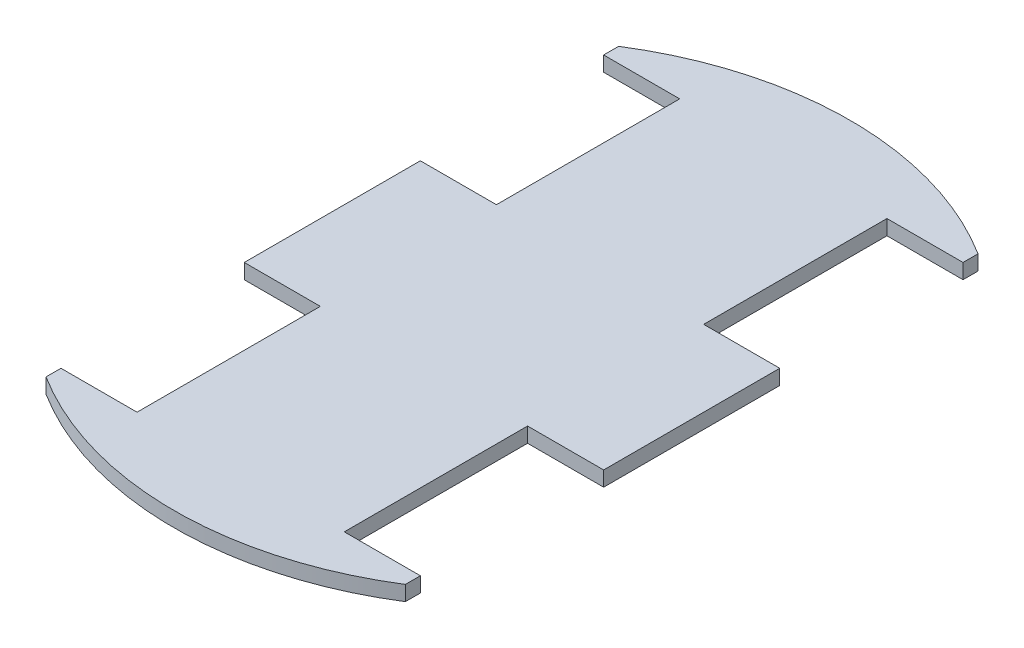
SolidWorks part; units mm, degrees
material "Oak"
ref_plane "Front Plane" through (0, 0, 0) normal (0, 0, 1) x (1, 0, 0)
ref_plane "Top Plane" through (0, 0, 0) normal (0, 1, 0) x (1, 0, 0)
ref_plane "Right Plane" through (0, 0, 0) normal (1, 0, 0) x (0, 0, -1)
sketch "Sketch1" plane through (0, 0, 0) normal (0, 1, 0) x (1, 0, 0)
  line L0 (50.292, 32.512) -> (76.2, 32.512) construction
  line L1 (-76.2, 32.512) -> (-50.292, 32.512) construction
  line L2 (-76.2, 32.512) -> (-76.2, -32.512) construction
  line L3 (-76.2, -32.512) -> (-50.292, -32.512) construction
  line L4 (-50.292, 32.512) -> (-50.292, -32.512) construction
  line L5 (-76.2, 32.512) -> (-50.292, -32.512) construction
  line L6 (-76.2, -32.512) -> (-50.292, 32.512) construction
  line L7 (50.292, 32.512) -> (50.292, -32.512) construction
  line L8 (50.292, -32.512) -> (76.2, -32.512) construction
  line L9 (76.2, 32.512) -> (76.2, -32.512) construction
  line L10 (50.292, 32.512) -> (76.2, -32.512) construction
  line L11 (50.292, -32.512) -> (76.2, 32.512) construction
  line L12 (-76.2, -119.888) -> (-50.292, -119.888) construction
  line L13 (-76.2, -119.888) -> (-76.2, -184.912) construction
  line L14 (-76.2, -184.912) -> (-50.292, -184.912) construction
  line L15 (-50.292, -119.888) -> (-50.292, -184.912) construction
  line L16 (-76.2, -119.888) -> (-50.292, -184.912) construction
  line L17 (-76.2, -184.912) -> (-50.292, -119.888) construction
  line L18 (50.292, -119.888) -> (76.2, -119.888) construction
  line L19 (50.292, -119.888) -> (50.292, -184.912) construction
  line L20 (50.292, -184.912) -> (76.2, -184.912) construction
  line L21 (76.2, -119.888) -> (76.2, -184.912) construction
  line L22 (50.292, -119.888) -> (76.2, -184.912) construction
  line L23 (50.292, -184.912) -> (76.2, -119.888) construction
  line L24 (-76.2, -38.862) -> (-43.942, -38.862)
  line L25 (-76.2, 0) -> (76.2, 0) construction
  line L26 (-76.2, 0) -> (-76.2, -152.4) construction
  line L27 (-76.2, -152.4) -> (76.2, -152.4) construction
  line L28 (76.2, 0) -> (76.2, -152.4) construction
  line L29 (-76.2, 0) -> (76.2, -152.4) construction
  line L30 (-76.2, -152.4) -> (76.2, 0) construction
  line L31 (-43.942, 38.862) -> (-43.942, -38.862)
  line L32 (-76.2, 38.862) -> (-43.942, 38.862)
  line L33 (43.942, -38.862) -> (76.2, -38.862)
  line L34 (43.942, 38.862) -> (43.942, -38.862)
  line L35 (43.942, 38.862) -> (76.2, 38.862)
  line L36 (43.942, -191.262) -> (76.2, -191.262)
  line L37 (43.942, -113.538) -> (43.942, -191.262)
  line L38 (43.942, -113.538) -> (76.2, -113.538)
  line L39 (-76.2, -191.262) -> (-43.942, -191.262)
  line L40 (-43.942, -113.538) -> (-43.942, -191.262)
  line L41 (-76.2, -113.538) -> (-43.942, -113.538)
  line L42 (-76.2, -113.538) -> (-76.2, -38.862)
  line L43 (76.2, -38.862) -> (76.2, -113.538)
  line L44 (-76.2, 38.862) -> (-76.2, 45.212)
  line L45 (76.2, 38.862) -> (76.2, 45.212)
  line L46 (-76.2, -191.262) -> (-76.2, -197.612)
  line L47 (76.2, -191.262) -> (76.2, -197.612)
  arc A0 (-76.2, 45.212) -> (76.2, 45.212) centre (0, -76.2) cw
  arc A1 (-76.2, -197.612) -> (76.2, -197.612) centre (0, -76.2) ccw
  point P4 (-63.246, 0)
  point P9 (63.246, 0)
  point P14 (-63.246, -152.4)
  point P19 (63.246, -152.4)
  point P24 (0, -76.2)
  dimension "D7" = 6.35
  dimension "D1" = 152.4
  dimension "D2" = 152.4
  dimension "D3" = 25.908
  dimension "D4" = 65.024
  dimension "D6" = 6.35
  dimension "D5" = 6.35
extrude "Chassis" add sketch "Sketch1" along normal blind 6.35
